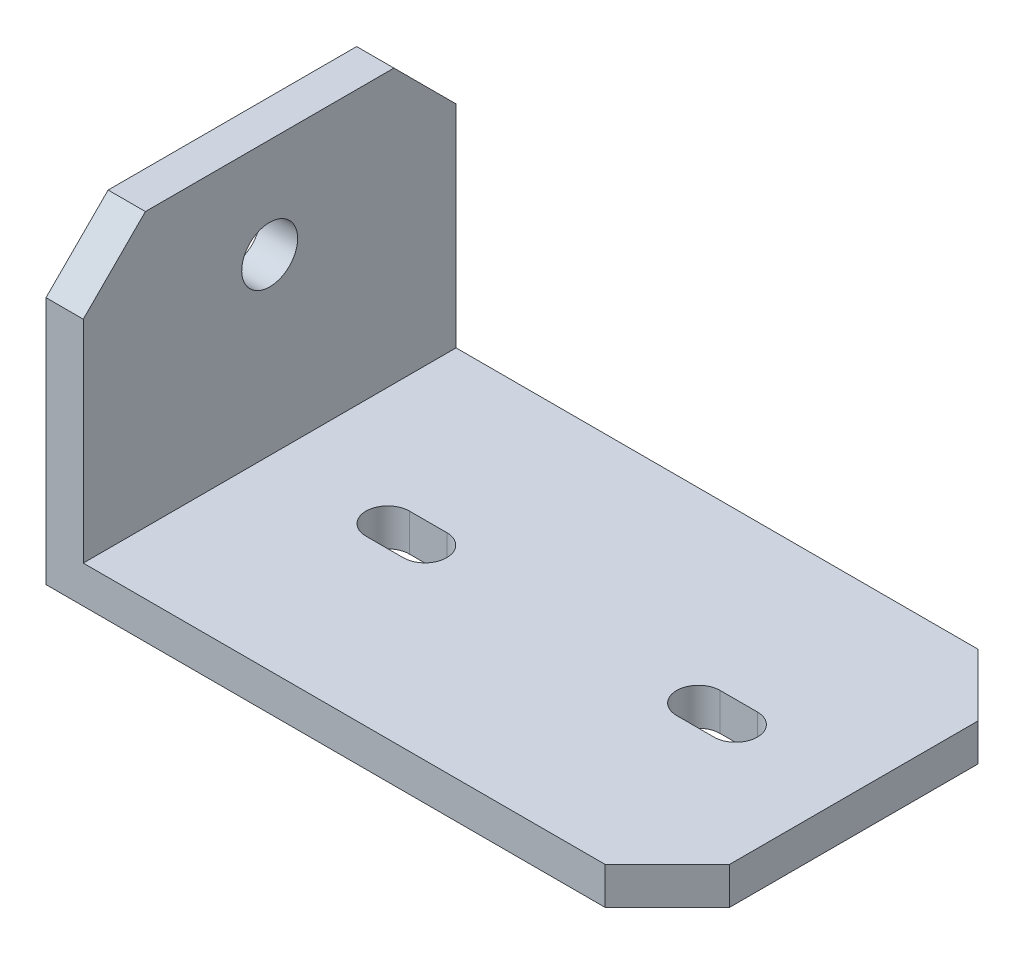
SolidWorks part; units mm, degrees
ref_plane "Front Plane" through (0, 0, 0) normal (0, 0, 1) x (1, 0, 0)
ref_plane "Top Plane" through (0, 0, 0) normal (0, 1, 0) x (1, 0, 0)
ref_plane "Right Plane" through (0, 0, 0) normal (1, 0, 0) x (0, 0, -1)
sketch "Sketch1" plane through (0, 0, 0) normal (0, 0, 1) x (1, 0, 0)
  line L0 (0, 22) -> (0, 0)
  line L1 (0, 0) -> (47, 0)
  line L2 (47, 0) -> (47, -3)
  line L3 (47, -3) -> (-3, -3)
  line L4 (-3, -3) -> (-3, 22)
  line L5 (-3, 22) -> (0, 22)
  dimension "D1" = 3
  dimension "D2" = 3
  dimension "D3" = 50
  dimension "D4" = 25
extrude "Boss-Extrude1" add sketch "Sketch1" along normal blind 30
sketch "Sketch2" plane through (0, 0, 0) normal (1, 0, 0) x (0, 0, -1)
  line L0 (-15, 0) -> (-15, 22) construction
  line L1 (-30, 0) -> (0, 0) construction
  line L2 (-30, 22) -> (0, 22) construction
  line L3 (-30, -3) -> (0, -3) construction
  circle A0 centre (-15, 14) radius 2.25
  point P10 (-15, -3)
  dimension "D2" = 4.5
  dimension "D1" = 17
extrude "Cut-Extrude1" cut sketch "Sketch2" against normal blind 30
sketch "Sketch3" plane through (0, 0, 0) normal (0, 1, 0) x (1, 0, 0)
  line L0 (0, -15) -> (11, -15) construction
  line L1 (0, -30) -> (0, 0) construction
  line L2 (11, -15) -> (36, -15) construction
  line L3 (36, -15) -> (47, -15) construction
  line L4 (47, -30) -> (47, 0) construction
  line L5 (9.5, -15) -> (12.5, -15) construction
  line L6 (9.5, -13.25) -> (12.5, -13.25)
  line L7 (9.5, -16.75) -> (12.5, -16.75)
  line L8 (34.5, -15) -> (37.5, -15) construction
  line L9 (34.5, -13.25) -> (37.5, -13.25)
  line L10 (34.5, -16.75) -> (37.5, -16.75)
  arc A0 (9.5, -13.25) -> (9.5, -16.75) centre (9.5, -15) ccw
  arc A1 (12.5, -16.75) -> (12.5, -13.25) centre (12.5, -15) ccw
  arc A2 (34.5, -13.25) -> (34.5, -16.75) centre (34.5, -15) ccw
  arc A3 (37.5, -16.75) -> (37.5, -13.25) centre (37.5, -15) ccw
  point P10 (11, -15)
  point P16 (36, -15)
  dimension "D1" = 1.75
  dimension "D2" = 25
  dimension "D4" = 3
  dimension "D3" = 11
extrude "Cut-Extrude2" cut sketch "Sketch3" against normal blind 30
chamfer "Chamfer1" distance 5 angle 45 4 edges at (-1.5, 22, 30) (-1.5, 22, 0) (47, -1.5, 30) (47, -1.5, 0)
